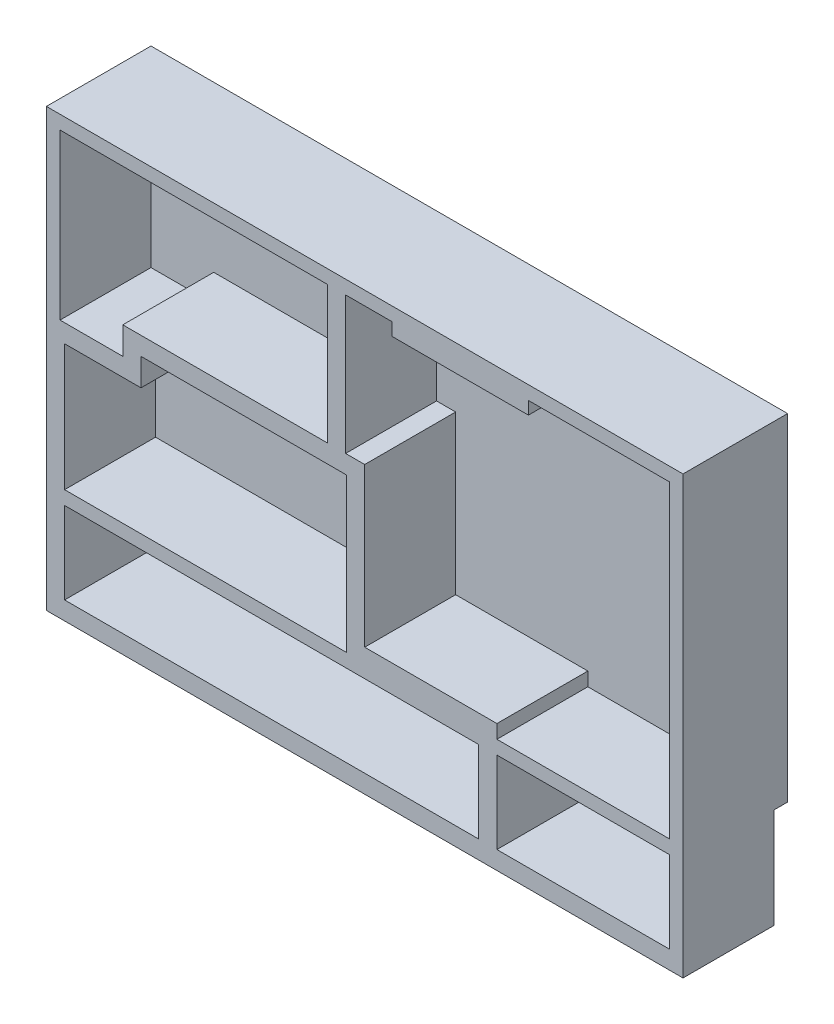
SolidWorks part; units mm, degrees
ref_plane "前视基准面" through (0, 0, 0) normal (0, 0, 1) x (1, 0, 0)
ref_plane "上视基准面" through (0, 0, 0) normal (0, 1, 0) x (1, 0, 0)
ref_plane "右视基准面" through (0, 0, 0) normal (1, 0, 0) x (0, 0, -1)
sketch "草图1" plane through (0, 0, 0) normal (0, 0, 1) x (1, 0, 0)
  line L1 (-35, 18.5) -> (35, 18.5)
  line L2 (-35, 18.5) -> (-35, -18.5)
  line L3 (-35, -18.5) -> (35, -18.5)
  line L4 (35, 18.5) -> (35, -18.5)
  line L5 (-35, 18.5) -> (35, -18.5) construction
  line L6 (-35, -18.5) -> (35, 18.5) construction
  point P0 (0, 0)
  dimension "D1" = 37
  dimension "D2" = 70
extrude "凸台-拉伸1" add sketch "草图1" along normal blind 11.5
shell "抽壳1" thickness 1.5 removed face at (0, 0, 11.5)
sketch "草图2" plane through (0, 0, 1.5) normal (0, 0, 1) x (1, 0, 0)
  line L0 (-26.6, 1.9) -> (-4.1, 1.9)
  line L1 (-33.5, 17) -> (-33.5, -17) construction
  line L2 (-2.1, 1.9) -> (0, 1.9)
  line L3 (0, 1.9) -> (0, -15.5)
  line L4 (0, -15.5) -> (14.536, -15.5)
  line L5 (14.536, -15.5) -> (14.536, -27.5)
  line L6 (13.5611, -29.5) -> (35, -29.5)
  line L7 (35, -29.5) -> (35, -18.5)
  line L8 (35, -18.5) -> (33.5, -18.5)
  line L9 (-35, -18.5) -> (35, -18.5) construction
  line L10 (33.5, -18.5) -> (33.5, -27.5)
  line L11 (33.5, -27.5) -> (14.536, -27.5)
  line L12 (12.536, -27.5) -> (12.536, -18.5)
  line L13 (12.536, -18.5) -> (-2, -18.5)
  line L14 (-2, -18.5) -> (-2, -0.1)
  line L15 (-2, -0.1) -> (-24.6, -0.1)
  line L17 (-4.1, 17) -> (-4.1, 1.9)
  line L18 (33.5, 17) -> (-33.5, 17) construction
  line L19 (-2.1, 17) -> (-2.1, 1.9)
  line L20 (-4.1, 17) -> (-2.1, 17)
  line L21 (3, 17) -> (3, 15.6)
  line L22 (3, 15.6) -> (18, 15.6)
  line L23 (18, 15.6) -> (18, 17)
  line L24 (18, 17) -> (3, 17)
  line L25 (35, -18.5) -> (35, 18.5) construction
  line L26 (13.5611, -29.5) -> (12.4, -29.5)
  line L29 (-4.2, 6.5) -> (-4.2, 12.5) construction
  line L30 (-6.2, 2) -> (-26.7, 2) construction
  line L31 (-26.6, 1.9) -> (-26.6, -1.1)
  line L32 (-26.6, -1.1) -> (-33.5, -1.1)
  line L34 (-33, -3.1) -> (-24.6, -3.1)
  line L35 (-24.6, -3.1) -> (-24.6, -0.1)
  line L36 (-26.7, -1) -> (-32.2, -1) construction
  line L37 (-26.7, -1) -> (-26.7, 2) construction
  line L38 (10.5, 17.25) -> (10.5, 14.3773) construction
  line L39 (11.5, 17.25) -> (9.5, 17.25) construction
  line L40 (-35, -18.5) -> (-35, -29.5)
  line L41 (-35, 18.5) -> (-35, -18.5) construction
  line L42 (-35, -29.5) -> (12.4, -29.5)
  line L43 (12.536, -27.5) -> (-33, -27.5)
  line L44 (-33, -27.5) -> (-33, -3.1)
  line L46 (-35, -1.1) -> (-35, -18.5)
  line L47 (-35, -1.1) -> (-33.5, -1.1)
  line L48 (14.636, -19.8) -> (14.636, -26.8) construction
  dimension "D1" = 1.5
  dimension "D2" = 2
  dimension "D3" = 0.1
  dimension "D4" = 9
  dimension "D5" = 2
  dimension "D6" = 3
  dimension "D7" = 2
  dimension "D8" = 2
  dimension "D9" = 0.1
  dimension "D10" = 2
  dimension "D11" = 0.1
  dimension "D12" = 2
  dimension "D13" = 2
  dimension "D14" = 0.1
  dimension "D15" = 0.1
  dimension "D16" = 1.4
  dimension "D17" = 15
  dimension "D18" = 2
extrude "凸台-拉伸2" add sketch "草图2" along normal up to surface (10 mm away) up to face at (0, 0, 11.5)
